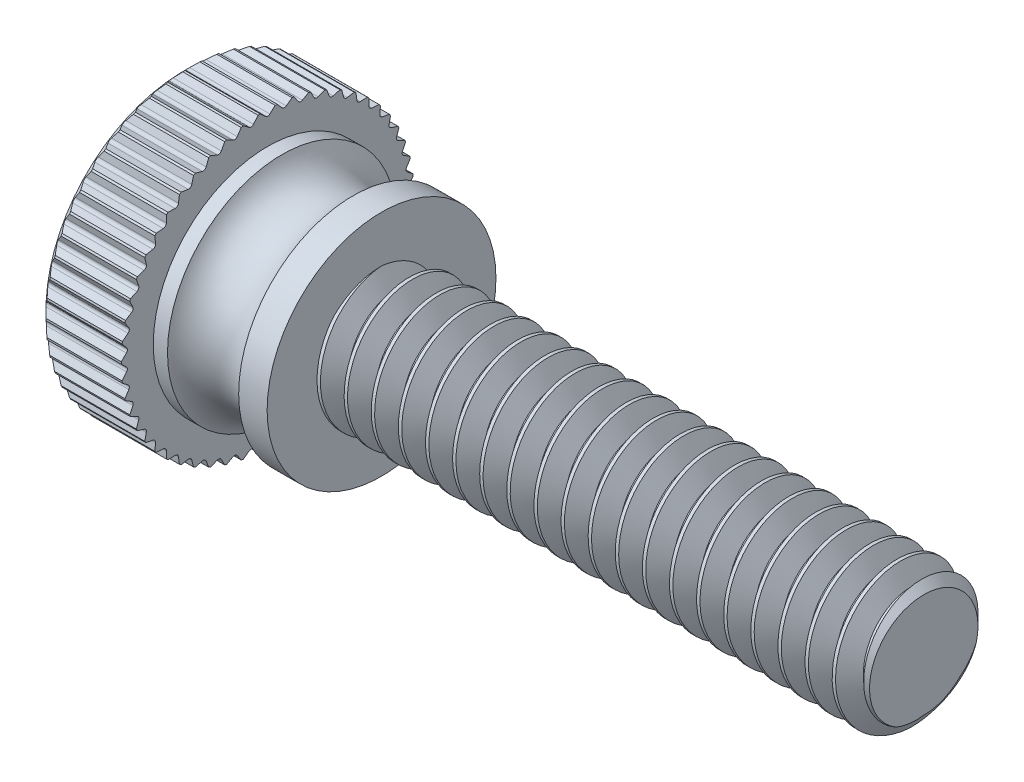
SolidWorks part; units mm, degrees
ref_plane "Front Plane" through (0, 0, 0) normal (0, 0, 1) x (1, 0, 0)
ref_plane "Top Plane" through (0, 0, 0) normal (0, 1, 0) x (1, 0, 0)
ref_plane "Right Plane" through (0, 0, 0) normal (1, 0, 0) x (0, 0, -1)
sketch "Sketch1" plane through (0, 0, 0) normal (0, 0, 1) x (1, 0, 0)
  line L0 (0, 0) -> (25.4, 0) construction
  line L1 (0, 0) -> (-9.271, 0) construction
  line L2 (-9.271, 6.858) -> (-9.271, -6.858) construction
  line L3 (25.4, 3.175) -> (25.4, -3.175) construction
  line L4 (0, 3.175) -> (0, -3.175) construction
  line L5 (-5.334, 5.3594) -> (-5.334, -5.3594) construction
  line L6 (-9.271, 6.858) -> (-5.334, 6.858) construction
  line L7 (25.4, 3.175) -> (24.13, 3.175) construction
  line L8 (-5.334, 5.3594) -> (0, 5.3594) construction
  line L9 (0, 3.175) -> (25.4, 3.175) construction
  line L10 (-9.271, -6.858) -> (-5.334, -6.858) construction
  line L11 (-5.334, -5.3594) -> (0, -5.3594) construction
  point P7 (25.4, 0)
  point P8 (0, 0)
  point P9 (-9.271, 0)
  point P16 (22.225, -3.175)
  point P17 (0, 0)
  point P21 (25.4, 0)
  point P22 (-9.271, 0)
  point P23 (-5.334, 0)
  dimension "Head Diameter" = 13.716
  dimension "Head Height" = 3.937
  dimension "Collar Diameter" = 10.7188
  dimension "Length" = 25.4
  dimension "Thread Pitch" = 1.27
  dimension "D2" = 3.175
  dimension "Overall Head Height" = 9.271
  dimension "Collar Height" = 5.334
  dimension "Screw Size Decimal Equivalent" = 6.35
sketch "Sketch2" plane through (0, 0, 0) normal (1, 0, 0) x (0, 0, -1)
  line L0 (0, 5.3594) -> (0, -5.3594) construction
  line L1 (-6.858, 0) -> (6.858, 0) construction
  line L2 (0, 6.858) -> (0, -6.858) construction
  circle A0 centre (0, 0) radius 6.858 construction
  circle A1 centre (0, 0) radius 5.3594 construction
  circle A2 centre (0, 0) radius 3.175 construction
  point P13 (0, -3.175)
  point P14 (3.175, 0)
  point P16 (0, 3.175)
  point P17 (-3.175, 0)
  point P18 (-5.3594, 0)
  point P19 (0, 5.3594)
  point P20 (5.3594, 0)
  point P21 (0, -5.3594)
  point P23 (0, -6.858)
  point P24 (6.858, 0)
  point P25 (0, 6.858)
  point P26 (-6.858, 0)
  point P27 (0, 0)
sketch "Sketch3" plane through (0, 0, 0) normal (0, 0, 1) x (1, 0, 0)
  line L0 (-9.271, 0) -> (-9.271, 6.858)
  line L1 (-9.271, 6.858) -> (-5.334, 6.858)
  line L2 (-5.334, 6.858) -> (-5.334, 5.3594)
  line L3 (-5.334, 5.3594) -> (-5.334, -5.3594) construction
  line L4 (-1.3335, 5.3594) -> (0, 5.3594)
  line L5 (0, -5.3594) -> (0, 5.3594) construction
  line L6 (0, 5.3594) -> (0, 3.175)
  line L7 (0, 3.175) -> (25.4, 3.175)
  line L8 (0, 3.175) -> (25.4, 3.175) construction
  line L10 (25.4, 3.175) -> (25.4, -3.175) construction
  line L11 (25.4, 3.175) -> (25.4, 0)
  line L12 (25.4, 0) -> (-9.271, 0)
  line L13 (-5.334, 5.3594) -> (-4.6673, 5.3594)
  line L14 (-5.334, 5.3594) -> (0, 5.3594) construction
  line L15 (-3.0004, 4.2875) -> (-3.0004, 5.3594) construction
  arc A1 (-4.6673, 5.3594) -> (-1.3335, 5.3594) centre (-3.0004, 6.1195) ccw
  dimension "D1" = 0.6667
  dimension "D2" = 1.3335
  dimension "D3" = 1.0719
revolve "Revolve1" add sketch "Sketch3" angle 360 about L0
chamfer "Chamfer1" distance 0.635 angle 45 1 edges at (25.4, 0, 3.175)
chamfer "Chamfer2" distance 0.4115 angle 45 1 edges at (-9.271, 0, 6.858)
split "Split1" trim tools "Right Plane" bodies to split 104 resulting bodies 105 106
sketch "Sketch4" plane through (25.4, 0, 0) normal (1, 0, 0) x (0, 0, -1)
  circle A0 centre (0, 0) radius 3.175
curve "Helix/Spiral1" pitch 1.27 height 26.67 turns 21
sketch "Sketch5" plane through (0, 0, 0) normal (0, 0, 1) x (1, 0, 0)
  line L0 (25.3206, 3.3125) -> (26.5906, 3.3125) construction
  line L1 (26.5906, 3.3125) -> (25.9556, 2.2126) construction
  line L2 (25.9556, 2.2126) -> (25.3206, 3.3125) construction
  line L3 (25.3603, 3.2437) -> (26.5509, 3.2437) construction
  line L4 (25.4, 3.175) -> (26.5112, 3.175) construction
  line L5 (25.8762, 2.3501) -> (26.035, 2.3501) construction
  line L6 (25.9556, 2.2126) -> (25.9556, 2.3501) construction
  line L7 (25.9556, 3.175) -> (25.9556, 3.3125) construction
  line L8 (25.3603, 3.2437) -> (26.5509, 3.2437)
  line L9 (26.5509, 3.2437) -> (26.035, 2.3501)
  line L10 (26.035, 2.3501) -> (25.8762, 2.3501)
  line L11 (25.8762, 2.3501) -> (25.3603, 3.2437)
  point P12 (25.9556, 3.2437)
  dimension "D1" = 1.27
  dimension "D2" = 0.1588
sweep "Cut-Sweep1" cut profiles "Sketch5" path "Helix/Spiral1" align with end faces yes
sketch "Sketch6" plane through (0, 0, 0) normal (1, 0, 0) x (0, 0, -1)
  circle A0 centre (0, 0) radius 3.175
  circle A1 centre (0, 0) radius 3.175 construction
extrude "Boss-Extrude1" add sketch "Sketch6" against normal through all draft 60
sketch "Sketch7" plane through (-9.271, 0, 0) normal (-1, 0, 0) x (0, 0, 1)
  line L0 (0, 0) -> (0.3594, 6.858) construction
  line L1 (0, 3.175) -> (0, -3.175) construction
  line L2 (0.3594, 6.858) -> (-0.3594, 6.858) construction
  line L3 (-0.3594, 6.858) -> (0, 0) construction
  line L4 (0, 0) -> (0, 6.858) construction
  line L5 (-0.6374, 7.112) -> (0.6374, 7.112)
  line L6 (0.6374, 7.112) -> (0, 6.5296) construction
  line L7 (0, 6.5296) -> (-0.6374, 7.112) construction
  line L8 (0, 6.5296) -> (0, 7.112) construction
  line L9 (-0.6374, 7.112) -> (-0.1029, 6.6236)
  line L10 (0.1029, 6.6236) -> (0.6374, 7.112)
  line L11 (0.1029, 6.6236) -> (-0.1029, 6.6236) construction
  line L12 (0, 6.858) -> (0, -6.858) construction
  circle A0 centre (0, 0) radius 6.858 construction
  arc A1 (-0.1029, 6.6236) -> (0.1029, 6.6236) centre (0, 6.7362) ccw
  point P16 (0, 6.5837)
  dimension "D1" = 6
  dimension "D2" = 0.2743
  dimension "D3" = 0.2057
  dimension "D4" = 0.254
extrude "Cut-Extrude1" cut sketch "Sketch7" against normal up to vertex (9.271 mm away) up to point (0, 6.858, 0)
pattern_circular "CirPattern1" count 54 over 360 about axis through (0, 0, 0) along (1, 0, 0) of "Cut-Extrude1"
equation "\"D2@Sketch1\"=\"Thread Pitch@Sketch1\"*2.5"
equation "\"D1@Sketch3\"=\"Collar Height@Sketch1\"*.125"
equation "\"D2@Sketch3\"=\"Collar Height@Sketch1\"*.25"
equation "\"D3@Sketch3\"=\"Collar Diameter@Sketch1\"*.1"
equation "\"D1@Chamfer1\"=\"Thread Pitch@Sketch1\"*.5"
equation "\"D1@Chamfer2\"=\"Head Diameter@Sketch1\"*.03"
equation "\"D4@Helix/Spiral1\"=\"Thread Pitch@Sketch1\""
equation "\"D3@Helix/Spiral1\"=\"Length@Sketch1\"+\"Thread Pitch@Sketch1\""
equation "\"D2@Sketch5\"=\"D1@Sketch5\"*.125"
equation "\"D1@Sketch5\"=\"Thread Pitch@Sketch1\""
equation "\"D2@Sketch7\"=\"Head Diameter@Sketch1\"*.02"
equation "\"D3@Sketch7\"=\"Head Diameter@Sketch1\"*.015"
equation "\"D1@CirPattern1\"=(360/\"D1@Sketch7\")*.9"
